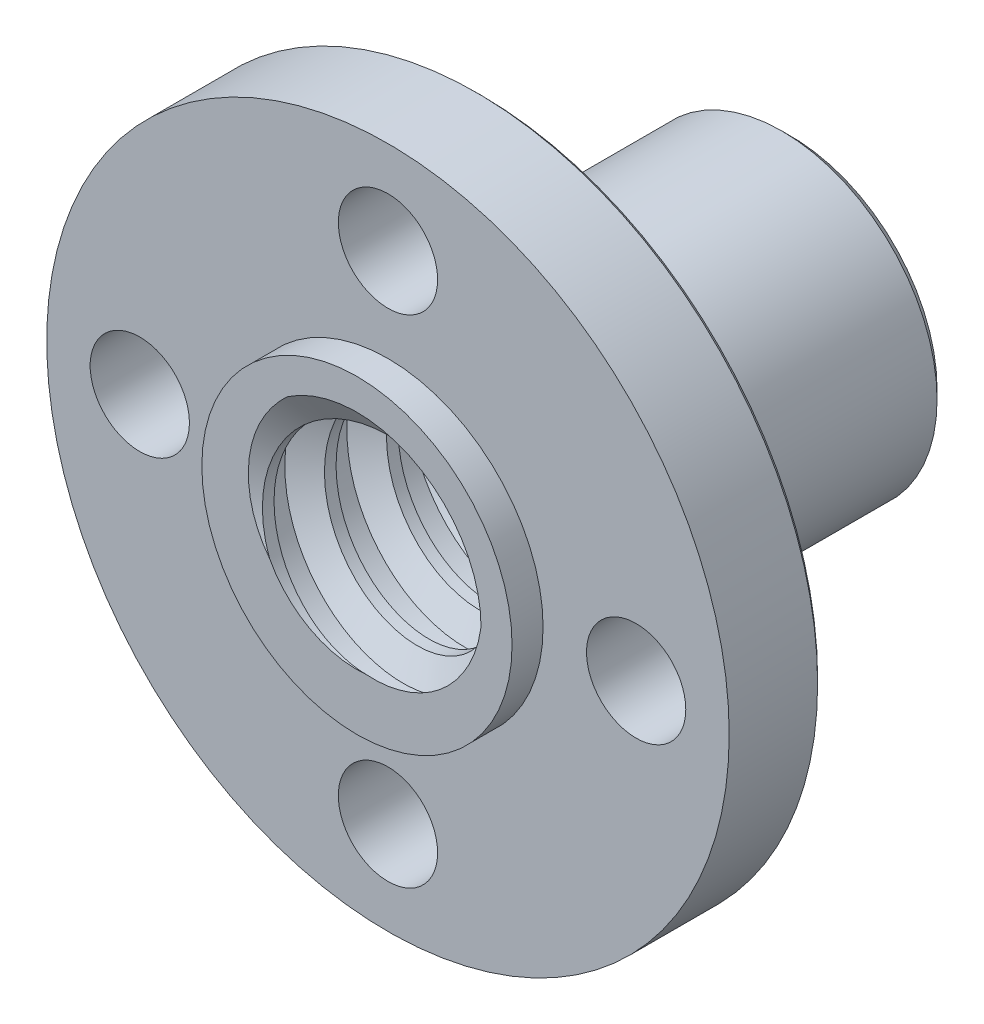
SolidWorks part; units mm, degrees
material "Brass"
ref_plane "正面" through (0, 0, 0) normal (0, 0, 1) x (1, 0, 0)
ref_plane "平面" through (0, 0, 0) normal (0, 1, 0) x (1, 0, 0)
ref_plane "右側面" through (0, 0, 0) normal (1, 0, 0) x (0, 0, -1)
sketch "Sketch1" plane through (0, 0, 0) normal (0, 0, 1) x (1, 0, 0)
  circle A0 centre (0, 0) radius 5
  dimension "D1" = 10
extrude "Boss-Extrude1" add sketch "Sketch1" along normal blind 14
sketch "Sketch3" plane through (0, 0, 0) normal (0, 0, -1) x (-1, 0, 0)
  circle A0 centre (0, 0) radius 4
  dimension "D1" = 8
extrude "Cut-Extrude1" cut sketch "Sketch3" against normal up to next
thread "Thread7" pitch 1.5 method extrude profile "Thread Profile5" start angle 0, offset 2, length 0, pitch 2, diameter 8
ref_plane "Plane5" through (4, 0, -2) normal (0, -1, 0) x (1, 0, 0)
sketch "Thread Profile5" plane through (4, 0, -2) normal (0, -1, 0) x (1, 0, 0)
  line L0 (0, 0) -> (0, 1.5) construction
  line L11 (0, 0) -> (0, 1.3125)
  line L12 (0, 1.3125) -> (-0.8119, 0.8437)
  line L13 (-0.8119, 0.8437) -> (-0.8119, 0.4687)
  line L15 (-0.8119, 0.4687) -> (0, 0)
  line L17 (-0.8119, 0.6562) -> (0, 0.6562) construction
  point P2 (0, 0)
  dimension "Pitch" = 1.5
  dimension "Profile_Angle" = 60
  dimension "Profile_Land" = 0.375
  dimension "Profile_Height" = 0.8119
sketch "Sketch14" plane through (0, 0, 0) normal (0, 0, -1) x (-1, 0, 0)
  circle A0 centre (0, 0) radius 5
extrude "Cut-Extrude2" cut sketch "Sketch14" along normal blind 14
sketch "Sketch15" plane through (0, 0, 14) normal (0, 0, 1) x (1, 0, 0)
  circle A0 centre (0, 0) radius 5
extrude "Cut-Extrude3" cut sketch "Sketch15" along normal blind 14
sketch "Sketch16" plane through (0, 0, 14) normal (0, 0, 1) x (1, 0, 0)
  circle A0 centre (0, 0) radius 11
  circle A1 centre (0, 0) radius 5 construction
  circle A2 centre (0, 0) radius 5
  dimension "D1" = 22
extrude "Boss-Extrude2" add sketch "Sketch16" against normal blind 3 from offset 1 offset against normal yes
sketch "Sketch17" plane through (0, 0, 13) normal (0, 0, 1) x (1, 0, 0)
  line L0 (0, 11) -> (0, -11) construction
  circle A0 centre (0, 0) radius 11 construction
  circle A1 centre (0, 8) radius 1.6
  circle A2 centre (8, 0) radius 1.6
  circle A3 centre (0, -8) radius 1.6
  circle A4 centre (-8, 0) radius 1.6
  point P17 (0, 0)
  dimension "D2" = 3.2
  dimension "D1" = 8
  dimension "D3" = 4
extrude "Cut-Extrude4" cut sketch "Sketch17" against normal up to next
chamfer "Chamfer1" distance 0.3 angle 45 1 edges at (5, 0, 0)
chamfer "Chamfer2" distance 0.15 angle 45 1 edges at (11, 0, 10)
